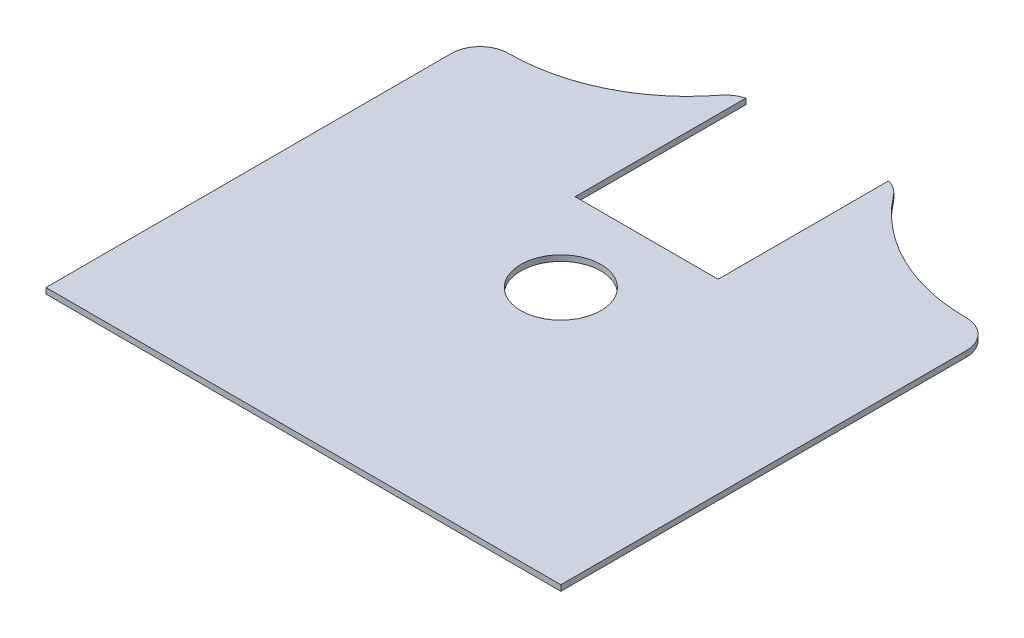
SolidWorks part; units mm, degrees
ref_plane "Front Plane" through (0, 0, 0) normal (0, 0, 1) x (1, 0, 0)
ref_plane "Top Plane" through (0, 0, 0) normal (0, 1, 0) x (1, 0, 0)
ref_plane "Right Plane" through (0, 0, 0) normal (1, 0, 0) x (0, 0, -1)
sketch "Sketch1" plane through (0, 0, 0) normal (0, 1, 0) x (1, 0, 0)
  line L1 (-90, -90) -> (90, -90)
  line L2 (-90, -90) -> (-90, 90)
  line L3 (-90, 90) -> (90, 90)
  line L4 (90, -90) -> (90, 90)
  line L5 (-90, -90) -> (90, 90) construction
  line L6 (-90, 90) -> (90, -90) construction
  point P0 (0, 0)
  dimension "D1" = 180
  dimension "D2" = 180
extrude "Boss-Extrude1" add sketch "Sketch1" along normal blind 2
sketch "Sketch2" plane through (0, 2, 0) normal (0, 1, 0) x (-1, 0, 0)
  line L0 (-90, 90) -> (-90, -90) construction
  line L5 (-90, -90) -> (90, -90) construction
  line L6 (90, -90) -> (90, 90) construction
  line L7 (22.4352, -90) -> (-22.2833, -90) construction
  line L8 (-22.2833, -90) -> (-90, -90)
  line L10 (90, -51.7417) -> (90, -90)
  line L11 (90, -90) -> (22.4352, -90)
  line L12 (-90, -90) -> (-90, -51.7418)
  line L13 (0.0759, -90) -> (0, 0) construction
  circle A0 centre (0, 0) radius 14
  arc A1 (30.3487, -86.1136) -> (79.9966, -61.7417) centre (79.975, -124.4523) cw
  arc A2 (-30.1969, -86.1136) -> (-79.9757, -61.7417) centre (-79.8232, -124.4522) ccw
  arc A3 (-90, -51.7418) -> (-79.9757, -61.7417) centre (-80, -51.7418) ccw
  arc A4 (-30.1969, -86.1136) -> (-22.2833, -90) centre (-22.2833, -80) ccw
  arc A5 (22.4352, -90) -> (30.3487, -86.1136) centre (22.4352, -80) ccw
  arc A6 (79.9966, -61.7417) -> (90, -51.7417) centre (80, -51.7417) ccw
  point P29 (-27.4241, -90)
  point P32 (27.5759, -90)
  point P35 (90, -62.5482)
  dimension "D1" = 28
  dimension "D4" = 10
  dimension "D3" = 55
extrude "Cut-Extrude1" cut sketch "Sketch2" against normal blind 2
sketch "Sketch4" plane through (0, 2, 0) normal (0, 1, 0) x (1, 0, 0)
  line L1 (25, 30) -> (-25, 30)
  line L2 (25, 30) -> (25, 90)
  line L3 (25, 90) -> (-25, 90)
  line L4 (-25, 30) -> (-25, 90)
  line L5 (25, 30) -> (-25, 90) construction
  line L6 (25, 90) -> (-25, 30) construction
  point P0 (0, 60)
  dimension "D1" = 60
  dimension "D2" = 50
extrude "Cut-Extrude2" cut sketch "Sketch4" against normal blind 2
